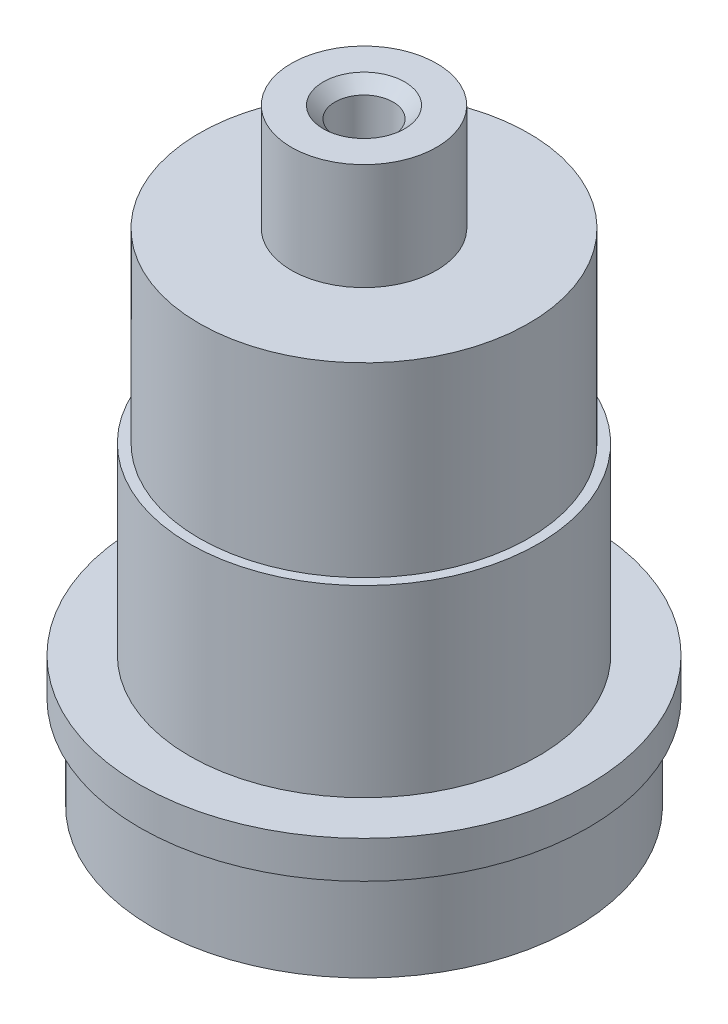
SolidWorks part; units mm, degrees
material "6061-T6 (SS)"
ref_plane "Front Plane" through (0, 0, 0) normal (0, 0, 1) x (1, 0, 0)
ref_plane "Top Plane" through (0, 0, 0) normal (0, 1, 0) x (1, 0, 0)
ref_plane "Right Plane" through (0, 0, 0) normal (1, 0, 0) x (0, 0, -1)
sketch "Sketch1" plane through (0, 0, 0) normal (0, 1, 0) x (1, 0, 0)
  circle A0 centre (0, 0) radius 23.0505
  dimension "D1" = 46.101
extrude "Boss-Extrude1" add sketch "Sketch1" along normal blind 10.16
sketch "Sketch2" plane through (0, 10.16, 0) normal (0, 1, 0) x (1, 0, 0)
  circle A0 centre (0, 0) radius 24.4856
  dimension "D1" = 48.9712
extrude "Boss-Extrude2" add sketch "Sketch2" along normal blind 4.064
sketch "Sketch3" plane through (0, 14.224, 0) normal (0, 1, 0) x (1, 0, 0)
  circle A0 centre (0, 0) radius 19.05
  dimension "D1" = 38.1
extrude "Boss-Extrude3" add sketch "Sketch3" along normal blind 20.066
sketch "Sketch4" plane through (0, 34.29, 0) normal (0, 1, 0) x (1, 0, 0)
  circle A0 centre (0, 0) radius 17.9959
  dimension "D1" = 35.9918
extrude "Boss-Extrude4" add sketch "Sketch4" along normal blind 20.32
sketch "Sketch5" plane through (0, 54.61, 0) normal (0, 1, 0) x (1, 0, 0)
  circle A0 centre (0, 0) radius 7.9375
  dimension "D1" = 15.875
extrude "Boss-Extrude5" add sketch "Sketch5" along normal blind 11.6332
sketch "Sketch6" plane through (0, 0, 0) normal (0, 0, 1) x (1, 0, 0)
  line L0 (6.35, 66.2432) -> (6.35, 67.7672)
  line L1 (7.9375, 66.2432) -> (-7.9375, 66.2432) construction
  line L2 (6.35, 67.7672) -> (3.3655, 67.7672)
  line L3 (3.3655, 67.7672) -> (3.3655, 71.8312)
  line L4 (3.3655, 71.8312) -> (7.112, 71.8312)
  line L5 (7.112, 71.8312) -> (7.112, 76.1492)
  line L6 (7.112, 76.1492) -> (0, 76.1492)
  line L7 (0, 76.1492) -> (0, 66.2432)
  line L8 (0, 66.2432) -> (6.35, 66.2432)
  dimension "D1" = 6.35
  dimension "D2" = 1.524
  dimension "D3" = 4.064
  dimension "D4" = 4.318
  dimension "D5" = 7.112
  dimension "D6" = 3.3655
revolve "Revolve1" [suppressed] add sketch "Sketch6" angle 360 about L7
fillet "Fillet1" [suppressed] radius 1.27
sketch "Sketch7" plane through (0, 66.2432, 0) normal (0, 1, 0) x (1, 0, 0)
  circle A0 centre (0, 0) radius 3.175
  dimension "D1" = 6.35
extrude "Cut-Extrude1" cut sketch "Sketch7" against normal blind 17.018
chamfer "Chamfer1" distance 1.27 angle 45 1 edges at (0, 66.2432, 3.175)
